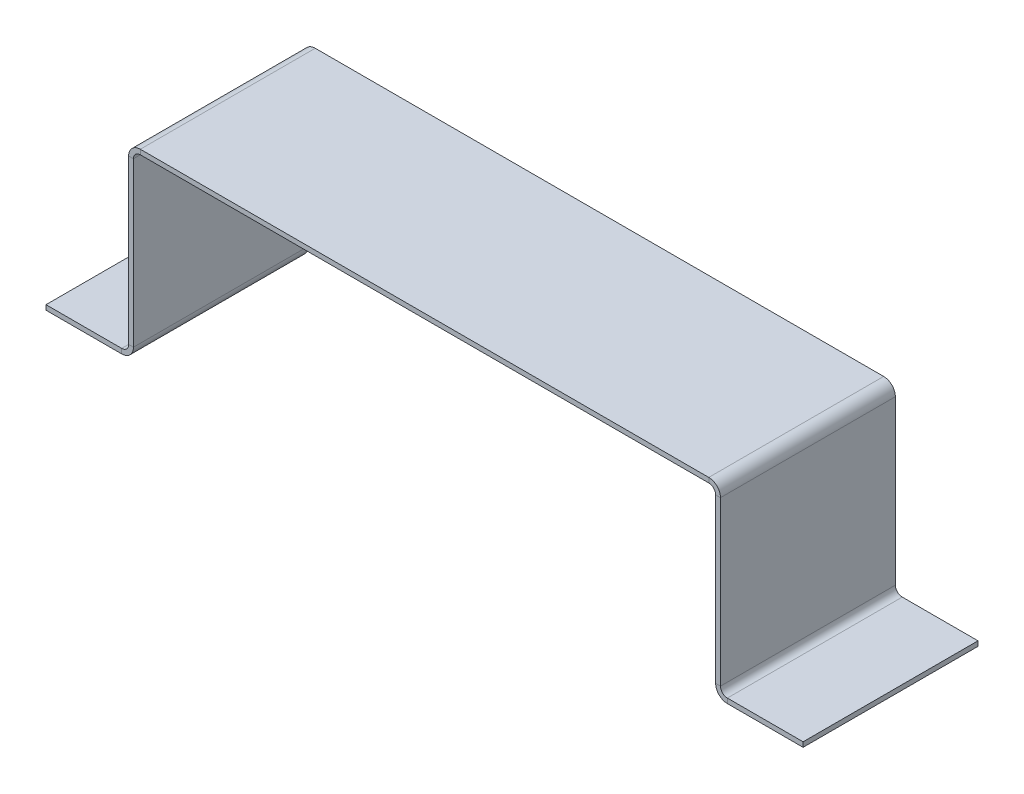
SolidWorks part; units mm, degrees
note: The reader was unsure of these and kept them because the rebuilt part matched: flange length of "Edge-Flange1", "Edge-Flange2", "Edge-Flange3", "Edge-Flange4".
ref_plane "Front Plane" through (0, 0, 0) normal (0, 0, 1) x (1, 0, 0)
ref_plane "Top Plane" through (0, 0, 0) normal (0, 1, 0) x (1, 0, 0)
ref_plane "Right Plane" through (0, 0, 0) normal (1, 0, 0) x (0, 0, -1)
sketch "Sketch1" plane through (0, 0, 0) normal (0, 1, 0) x (1, 0, 0)
  line L1 (-41.275, -12.7) -> (41.275, -12.7)
  line L2 (-41.275, -12.7) -> (-41.275, 12.7)
  line L3 (-41.275, 12.7) -> (41.275, 12.7)
  line L4 (41.275, -12.7) -> (41.275, 12.7)
  line L5 (-41.275, -12.7) -> (41.275, 12.7) construction
  line L6 (-41.275, 12.7) -> (41.275, -12.7) construction
  point P0 (0, 0)
  dimension "D1" = 25.4
  dimension "D2" = 82.55
base flange "Base-Flange1" sketch "Sketch1" thickness 0.7 reverse thickness direction no parameters "D1"=1
edge flange "Edge-Flange1" sketch "Sketch8" flange angle 90 flange length 25.4 flange position bend outside bend radius 1 thickness 0.7 relief rectangular parameters "D6"=0
sketch "Sketch8" plane through (41.275, -0.7, 0) normal (-1, 0, 0) x (0, 0, -1)
  line L2 (-12.7, 0) -> (-12.7, 24.7)
  line L3 (-12.7, 24.7) -> (12.7, 24.7)
  line L4 (12.7, 24.7) -> (12.7, 0)
  line L6 (12.7, 0) -> (-12.7, 0) construction
  line L7 (12.7, 0) -> (-12.7, 0)
bend "EdgeBend1" bend radius 1 bend angle 90 parameters "D5"=1
edge flange "Edge-Flange2" sketch "Sketch11" flange angle 90 flange length 12.7 flange position bend outside bend radius 1 thickness 0.7 relief rectangular parameters "D6"=0
sketch "Sketch11" plane through (42.975, -25.4, 0) normal (0, -1, 0) x (0, 0, -1)
  line L0 (12.7, 0) -> (-12.7, 0) construction
  line L1 (12.7, 0) -> (-12.7, 0)
  line L2 (-12.7, 0) -> (-12.7, 12)
  line L3 (-12.7, 12) -> (12.7, 12)
  line L4 (12.7, 12) -> (12.7, 0)
bend "EdgeBend2" bend radius 1 bend angle 90 parameters "D5"=2
edge flange "Edge-Flange3" sketch "Sketch15" flange angle 90 flange length 25.4 flange position bend outside bend radius 1 thickness 0.7 relief rectangular parameters "D6"=0
sketch "Sketch15" plane through (-41.275, -0.7, 0) normal (1, 0, 0) x (0, 0, 1)
  line L1 (12.7, 0) -> (-12.7, 0) construction
  line L2 (-12.7, 0) -> (-12.7, 24.7)
  line L3 (-12.7, 24.7) -> (12.7, 24.7)
  line L4 (12.7, 24.7) -> (12.7, 0)
  line L5 (12.7, 0) -> (-12.7, 0)
bend "EdgeBend3" bend radius 1 bend angle 90 parameters "D5"=3
edge flange "Edge-Flange4" sketch "Sketch18" flange angle 90 flange length 12.7 flange position bend outside bend radius 1 thickness 0.7 relief rectangular parameters "D6"=0
sketch "Sketch18" plane through (-42.975, -25.4, 0) normal (0, 1, 0) x (0, 0, -1)
  line L1 (12.7, 0) -> (-12.7, 0) construction
  line L2 (-12.7, 0) -> (-12.7, 12)
  line L3 (-12.7, 12) -> (12.7, 12)
  line L4 (12.7, 12) -> (12.7, 0)
  line L5 (12.7, 0) -> (-12.7, 0)
bend "EdgeBend4" bend radius 1 bend angle 90 parameters "D5"=4
sketch "Bend-Lines1" [suppressed] plane through (0, 0, 0) normal (0, 1, 0) x (1, 0, 0)
sketch "Bounding-Box1" [suppressed] plane through (0, 0, 0) normal (0, 1, 0) x (1, 0, 0)
sheet metal parameters "Sheet-Metal1" thickness 0.7 parameters "D1"=1
flat pattern "Flat-Pattern1" [suppressed]
sketch "Bend-Lines2" plane through (0, 0, 0) normal (0, 1, 0) x (1, 0, 0)
sketch "Bounding-Box2" [suppressed] plane through (0, 0, 0) normal (0, 1, 0) x (1, 0, 0)
sheet metal parameters "Sheet-Metal2" thickness 0.7 parameters "D1"=1
flat pattern "Flat-Pattern1" [suppressed]
sketch "Bend-Lines2" plane through (0, 0, 0) normal (0, 1, 0) x (1, 0, 0)
sketch "Bounding-Box2" [suppressed] plane through (0, 0, 0) normal (0, 1, 0) x (1, 0, 0)
bend of the flat pattern "Flatten-<EdgeBend1>1"
sheet metal parameters "Sheet-Metal3" thickness 0.7 parameters "D1"=1
flat pattern "Flat-Pattern1" [suppressed]
sketch "Bend-Lines2" plane through (0, 0, 0) normal (0, 1, 0) x (1, 0, 0)
  line L0 (55.4559, -12.7) -> (55.4559, 12.7) construction
  line L1 (42.3353, -12.7) -> (42.3353, 12.7) construction
  line L2 (55.4559, -12.7) -> (55.4559, 12.7) construction
  line L3 (42.3353, -12.7) -> (42.3353, 12.7) construction
sketch3d "Bounding-Box2" [suppressed]
  line L0 (67.5162, 12.7, 0) -> (-41.275, 12.7, 0) construction
  line L1 (67.5162, -12.7, 0) -> (-41.275, -12.7, 0) construction
  line L2 (67.5162, 12.7, 0) -> (67.5162, -12.7, 0) construction
  line L3 (-41.275, 12.7, 0) -> (-41.275, -12.7, 0) construction
bend of the flat pattern "Flatten-<EdgeBend1>1"
bend of the flat pattern "Flatten-<EdgeBend2>1"
sheet metal parameters "Sheet-Metal4" thickness 0.7 parameters "D1"=1
flat pattern "Flat-Pattern1" [suppressed]
sketch "Bend-Lines2" plane through (0, 0, 0) normal (0, 1, 0) x (1, 0, 0)
  line L0 (55.4559, -12.7) -> (55.4559, 12.7) construction
  line L1 (42.3353, -12.7) -> (42.3353, 12.7) construction
  line L2 (55.4559, -12.7) -> (55.4559, 12.7) construction
  line L3 (42.3353, -12.7) -> (42.3353, 12.7) construction
sketch3d "Bounding-Box2" [suppressed]
  line L0 (67.5162, 12.7, 0) -> (-41.275, 12.7, 0) construction
  line L1 (67.5162, -12.7, 0) -> (-41.275, -12.7, 0) construction
  line L2 (67.5162, 12.7, 0) -> (67.5162, -12.7, 0) construction
  line L3 (-41.275, 12.7, 0) -> (-41.275, -12.7, 0) construction
bend of the flat pattern "Flatten-<EdgeBend1>1"
bend of the flat pattern "Flatten-<EdgeBend3>1"
bend of the flat pattern "Flatten-<EdgeBend2>1"
sheet metal parameters "Sheet-Metal5" thickness 0.7 parameters "D1"=1
flat pattern "Flat-Pattern1"
sketch "Bend-Lines2" plane through (0, 0, 0) normal (0, 1, 0) x (1, 0, 0)
  line L0 (68.1559, -12.7) -> (68.1559, 12.7) construction
  line L1 (42.3353, -12.7) -> (42.3353, 12.7) construction
  line L2 (68.1559, -12.7) -> (68.1559, 12.7) construction
  line L3 (42.3353, -12.7) -> (42.3353, 12.7) construction
  line L4 (-68.1559, 12.7) -> (-68.1559, -12.7) construction
  line L5 (-42.3353, 12.7) -> (-42.3353, -12.7) construction
  line L6 (-68.1559, 12.7) -> (-68.1559, -12.7) construction
  line L7 (-42.3353, 12.7) -> (-42.3353, -12.7) construction
sketch3d "Bounding-Box2" [suppressed]
  line L0 (80.2162, 12.7, 0) -> (-80.2162, 12.7, 0) construction
  line L1 (80.2162, -12.7, 0) -> (-80.2162, -12.7, 0) construction
  line L2 (80.2162, 12.7, 0) -> (80.2162, -12.7, 0) construction
  line L3 (-80.2162, 12.7, 0) -> (-80.2162, -12.7, 0) construction
bend of the flat pattern "Flatten-<EdgeBend1>1"
bend of the flat pattern "Flatten-<EdgeBend3>1"
bend of the flat pattern "Flatten-<EdgeBend4>1"
bend of the flat pattern "Flatten-<EdgeBend2>1"
